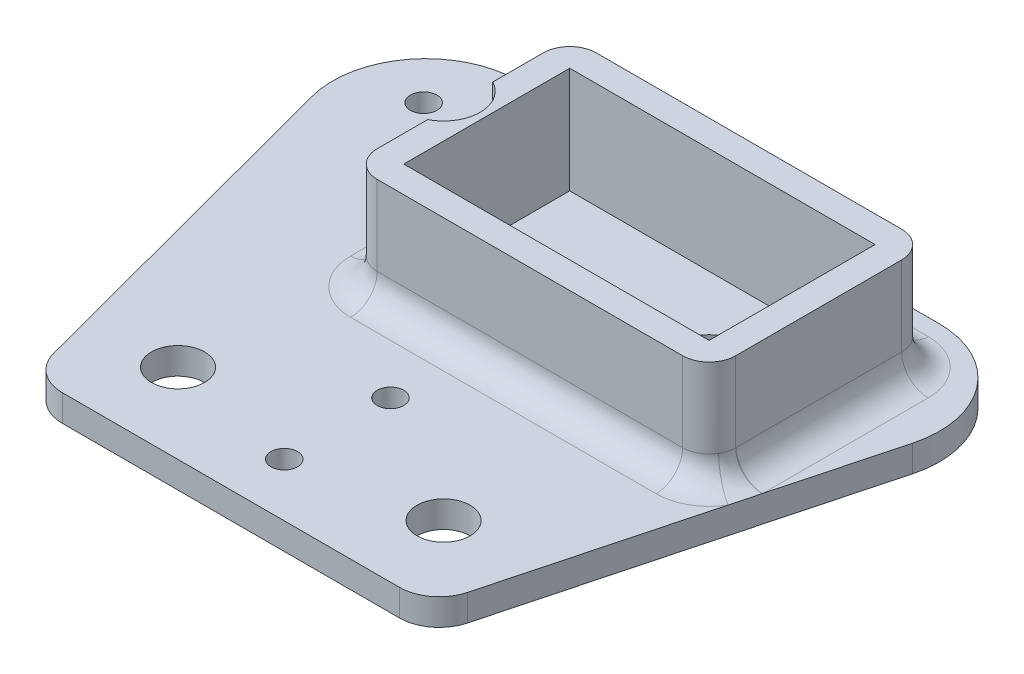
SolidWorks part; units mm, degrees
ref_plane "Front Plane" through (0, 0, 0) normal (0, 0, 1) x (1, 0, 0)
ref_plane "Top Plane" through (0, 0, 0) normal (0, 1, 0) x (1, 0, 0)
ref_plane "Right Plane" through (0, 0, 0) normal (1, 0, 0) x (0, 0, -1)
sketch "Sketch1" plane through (0, 0, 0) normal (0, 1, 0) x (1, 0, 0)
  line L0 (-56.6381, 0) -> (59.9343, 0) construction
  line L1 (0, 76.0508) -> (0, -42.0716) construction
  line L3 (15, 0) -> (24.9488, 37.5)
  line L4 (24.9488, 37.5) -> (-24.9488, 37.5)
  line L5 (-24.9488, 37.5) -> (-15, 0)
  line L6 (10, -35.718) -> (10, 52.392) construction
  line L7 (-58.5565, 6) -> (66.0263, 6) construction
  line L8 (-56.7778, 26) -> (55.9498, 26) construction
  line L9 (-14.995, -0.0189) -> (14.995, -0.0189)
  line L10 (-15, 0) -> (-14.995, -0.0189)
  line L11 (15, 0) -> (14.995, -0.0189)
  circle A0 centre (10, 26) radius 3
  circle A1 centre (10, 6) radius 2
  circle A2 centre (-10, 6) radius 2
  circle A4 centre (10, 26) radius 11.5 construction
  dimension "D7" = 6
  dimension "D5" = 23
  dimension "D6" = 4
  dimension "D1" = 10
  dimension "D2" = 30
  dimension "D3" = 6
  dimension "D4" = 20
extrude "Boss-Extrude1" add sketch "Sketch1" along normal blind 2
fillet "Fillet1" radius 7 2 edges at (24.9488, 1, -37.5) (-24.9488, 1, -37.5)
sketch "Sketch3" plane through (0, 2, 0) normal (0, 1, 0) x (1, 0, 0)
  line L0 (-10, 26) -> (42.6633, 26) construction
  line L1 (10, 26) -> (10, 52.4248) construction
  line L2 (-6.75, 19.75) -> (16.25, 19.75)
  line L3 (-6.75, 19.75) -> (-6.75, 32.25)
  line L4 (-6.75, 32.25) -> (16.25, 32.25)
  line L5 (16.25, 19.75) -> (16.25, 32.25)
  line L6 (-8.75, 34.25) -> (18.25, 34.25)
  line L7 (18.25, 17.75) -> (18.25, 34.25)
  line L8 (-8.75, 17.75) -> (18.25, 17.75)
  line L9 (-8.75, 17.75) -> (-8.75, 34.25)
  dimension "D1" = 12.5
  dimension "D2" = 23
  dimension "D3" = 6.25
  dimension "D4" = 2
extrude "Boss-Extrude2" add sketch "Sketch3" along normal blind 8
fillet "Fillet2" radius 2 4 edges at (-8.75, 6, -17.75) (18.25, 6, -17.75) (18.25, 6, -34.25) (-8.75, 6, -34.25)
fillet "Fillet3" radius 2 8 edges at (-8.1642, 2, -33.6642) (4.75, 2, -34.25) (17.6642, 2, -33.6642) (18.25, 2, -26) (17.6642, 2, -18.3358) (4.75, 2, -17.75) (-8.1642, 2, -18.3358) (-8.75, 2, -26)
sketch "Sketch2" plane through (0, 2, 0) normal (0, 1, 0) x (1, 0, 0)
  line L0 (0, -18.0124) -> (0, 52.2423) construction
  line L1 (-42.0895, 12) -> (41.773, 12) construction
  line L2 (-47.0474, 32.5) -> (41.773, 32.5) construction
  line L3 (-9.615, 0) -> (9.615, 0) construction
  line L4 (15.8495, 37.5) -> (-15.8495, 37.5) construction
  line L5 (10, 26) -> (-43.4257, 26) construction
  circle A0 centre (10, 26) radius 10 construction
  circle A1 centre (0, 34.5) radius 1
  circle A3 centre (18, 32.5) radius 1
  circle A4 centre (0, 4) radius 1
  circle A6 centre (0, 12) radius 1
  circle A8 centre (-18, 32.5) radius 1
  dimension "D1" = 20
  dimension "D4" = 2
  dimension "D5" = 2
  dimension "D7" = 2
  dimension "D8" = 2
  dimension "D2" = 12
  dimension "D3" = 5
  dimension "D9" = 3
  dimension "D10" = 18
  dimension "D12" = 8
sketch "Sketch4" plane through (0, 2, 0) normal (0, 1, 0) x (1, 0, 0)
  line L0 (0, -8.7295) -> (0, 49.4996) construction
  line L1 (10, 26) -> (-59.7059, 26) construction
  circle A0 centre (-10, 26) radius 2
  dimension "D1" = 4
  dimension "D2" = 10
extrude "Cut-Extrude2" cut sketch "Sketch4" against normal through all both and the other way through all
sketch "Sketch5" plane through (0, 2, 0) normal (0, 1, 0) x (1, 0, 0)
  circle A0 centre (-10, 26) radius 2.75
  dimension "D1" = 5.5
extrude "Cut-Extrude3" cut sketch "Sketch5" along normal through all
fillet "Fillet4" radius 3 2 edges at (14.995, 1, 0.0189) (-14.995, 1, 0.0189)
extrude "Cut-Extrude4" cut sketch "Sketch2" against normal blind 10
